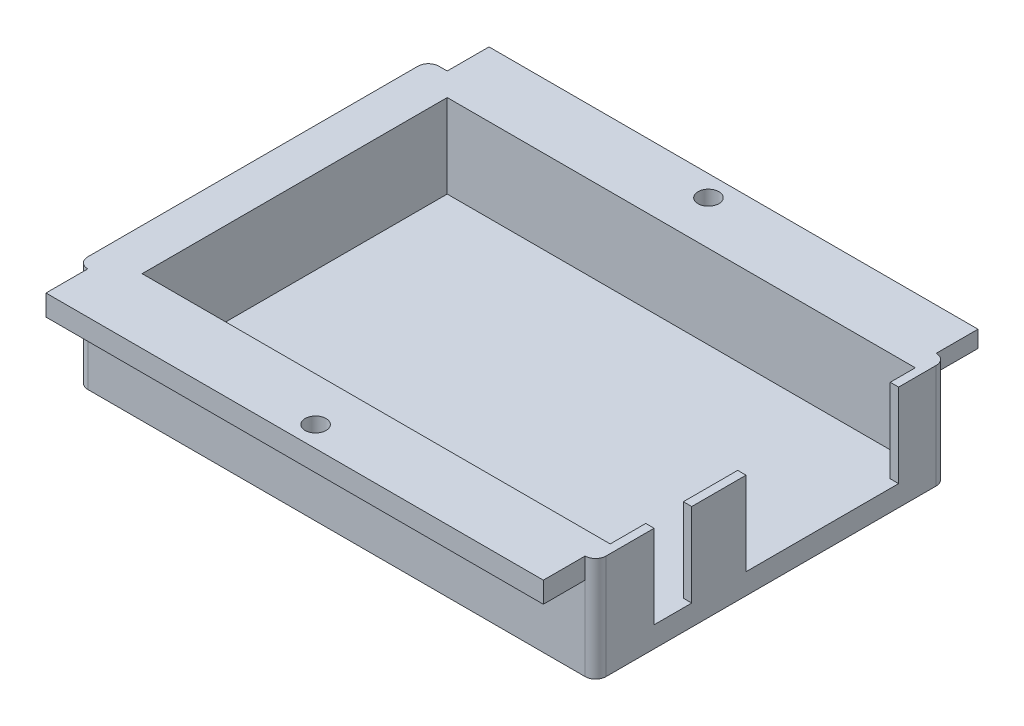
SolidWorks part; units mm, degrees
ref_plane "Front Plane" through (0, 0, 0) normal (0, 0, 1) x (1, 0, 0)
ref_plane "Top Plane" through (0, 0, 0) normal (0, 1, 0) x (1, 0, 0)
ref_plane "Right Plane" through (0, 0, 0) normal (1, 0, 0) x (0, 0, -1)
sketch "Sketch1" plane through (0, 0, 0) normal (0, 1, 0) x (1, 0, 0)
  line L1 (-62, -42) -> (62, -42)
  line L2 (-62, -42) -> (-62, 42)
  line L3 (-62, 42) -> (62, 42)
  line L4 (62, -42) -> (62, 42)
  line L5 (-62, -42) -> (62, 42) construction
  line L6 (-62, 42) -> (62, -42) construction
  point P0 (0, 0)
  dimension "D1" = 124
  dimension "D2" = 84
extrude "Boss-Extrude1" add sketch "Sketch1" along normal blind 25
sketch "Sketch2" plane through (0, 25, 0) normal (0, 1, 0) x (1, 0, 0)
  line L0 (-52, 36.5) -> (-52, -36.5)
  line L1 (-52, -36.5) -> (60, -36.5)
  line L3 (-52, 36.5) -> (60, 36.5)
  line L4 (60, -36.5) -> (60, 36.5)
  line L5 (62, -42) -> (62, 42) construction
  line L6 (0, -36.5) -> (0, 36.5) construction
  point P0 (0, 0)
  dimension "D1" = 112
  dimension "D2" = 73
  dimension "D3" = 2
extrude "Cut-Extrude1" cut sketch "Sketch2" against normal blind 20
sketch "Sketch3" plane through (0, 25, 0) normal (0, 1, 0) x (1, 0, 0)
  line L0 (-52, -36.5) -> (60, -36.5) construction
  line L1 (-62, -42) -> (62, -42) construction
  line L2 (60, -28) -> (62, -28)
  line L3 (60, -36.5) -> (60, 36.5) construction
  line L4 (62, -42) -> (62, 42) construction
  line L5 (62, -28) -> (62, -42)
  line L6 (62, -42) -> (60, -42)
  line L7 (60, -42) -> (60, -28)
  line L8 (62, 42) -> (62, 30.5)
  line L9 (62, 30.5) -> (60, 30.5)
  line L10 (60, -36.5) -> (60, 36.5) construction
  line L11 (60, 30.5) -> (60, 42)
  line L12 (62, 42) -> (-62, 42) construction
  line L13 (60, 42) -> (62, 42)
  dimension "D1" = 5.5
  dimension "D2" = 14
  dimension "D3" = 11.5
sketch "Sketch4" plane through (0, 25, 0) normal (0, 1, 0) x (1, 0, 0)
  line L0 (60, -28) -> (62, -28)
  line L1 (62, -28) -> (62, -19)
  line L2 (62, -42) -> (62, 42) construction
  line L3 (62, -19) -> (60, -19)
  line L4 (60, -36.5) -> (60, 36.5) construction
  line L5 (60, -19) -> (60, -28)
  line L6 (62, -42) -> (60, -42) construction
  line L7 (60, 30.5) -> (62, 30.5)
  line L8 (62, 30.5) -> (62, -6)
  line L9 (62, -6) -> (60, -6)
  line L10 (60, -36.5) -> (60, 36.5) construction
  line L11 (60, -6) -> (60, 30.5)
  line L12 (62, 42) -> (-62, 42) construction
  dimension "D1" = 23
  dimension "D2" = 48
extrude "Cut-Extrude2" cut sketch "Sketch4" against normal blind 20
fillet "Fillet1" radius 2.5 4 edges at (-62, 12.5, -42) (62, 12.5, -42) (62, 12.5, 42) (-62, 12.5, 42)
sketch "Sketch5" plane through (0, 0, 42) normal (0, 0, 1) x (1, 0, 0)
  line L0 (59.5, 0) -> (59.5, 25) construction
  line L1 (-59.5, 25) -> (59.5, 25)
  line L2 (-59.5, 25) -> (-59.5, 20)
  line L3 (-59.5, 20) -> (59.5, 20)
  line L4 (59.5, 25) -> (59.5, 20)
  dimension "D1" = 5
extrude "Boss-Extrude2" add sketch "Sketch5" along normal blind 10
sketch "Sketch6" plane through (0, 0, -42) normal (0, 0, -1) x (-1, 0, 0)
  line L1 (-59.5, 25) -> (57.5, 25)
  line L2 (-59.5, 25) -> (-59.5, 21)
  line L3 (-59.5, 21) -> (57.5, 21)
  line L4 (57.5, 25) -> (57.5, 21)
  dimension "D1" = 4
  dimension "D2" = 117
extrude "Boss-Extrude3" add sketch "Sketch6" along normal blind 10
sketch "Sketch7" plane through (0, 25, 0) normal (0, 1, 0) x (1, 0, 0)
  line L0 (-57.5, 52) -> (59.5, 52) construction
  line L1 (59.5, -52) -> (-59.5, -52) construction
  line L4 (-62, 39.5) -> (-62, -39.5) construction
  circle A0 centre (0, 47) radius 2.5
  circle A1 centre (0, -47) radius 2.5
  point P8 (0, -52)
  point P11 (0, 0)
  dimension "D1" = 5
  dimension "D4" = 5
  dimension "D2" = 5
  dimension "D3" = 62
extrude "Cut-Extrude3" cut sketch "Sketch7" against normal through all
